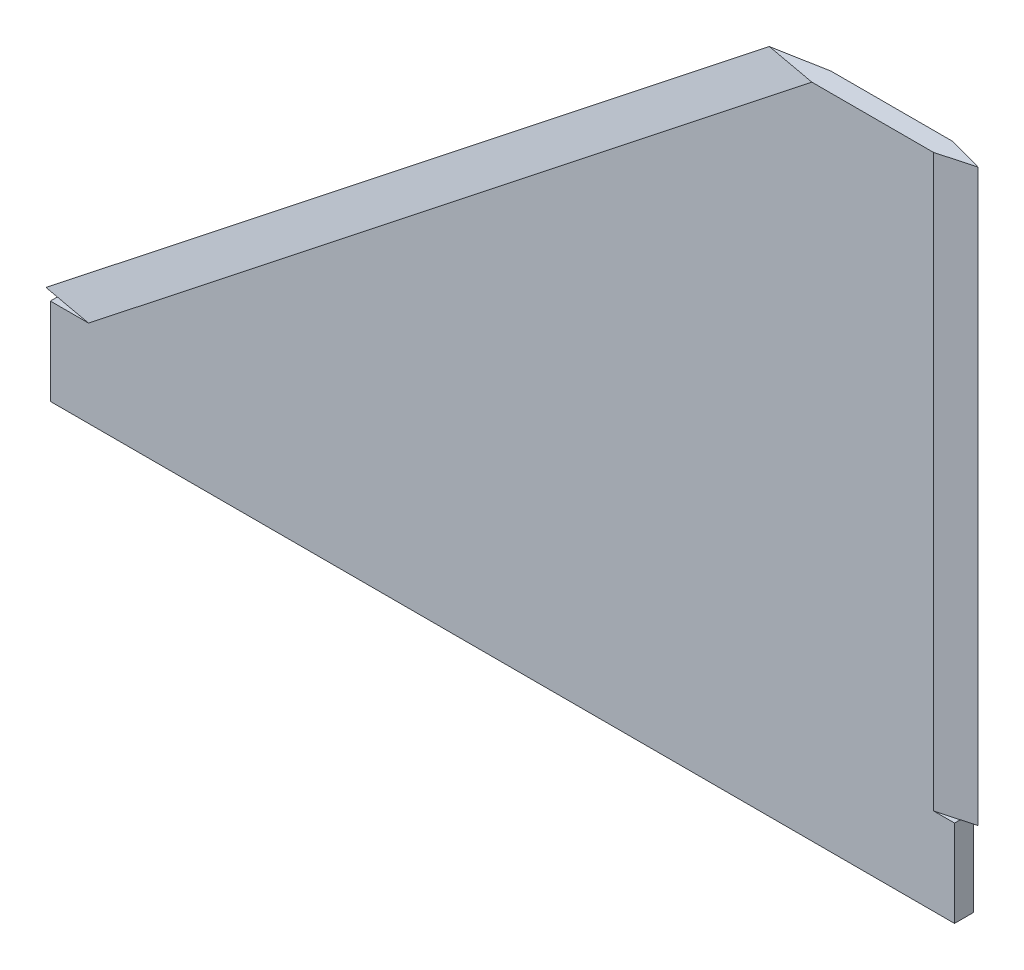
SolidWorks part; units mm, degrees
material "Hexcel AS4C (3000 Filaments)"
ref_plane "Front Plane" through (0, 0, 0) normal (0, 0, 1) x (1, 0, 0)
ref_plane "Top Plane" through (0, 0, 0) normal (0, 1, 0) x (1, 0, 0)
ref_plane "Right Plane" through (0, 0, 0) normal (1, 0, 0) x (0, 0, -1)
sketch "Sketch1" plane through (0, 0, 0) normal (0, 0, 1) x (1, 0, 0)
  line L0 (-130, 0) -> (-134, 0)
  line L1 (-130, -25) -> (130, -25)
  line L2 (-130, -25) -> (-130, 0)
  line L4 (130, -25) -> (130, 0)
  line L5 (-134, 0) -> (74, 164)
  line L6 (74, 164) -> (134, 164)
  line L7 (134, 164) -> (134, 0)
  line L8 (134, 0) -> (130, 0)
  line L9 (-130, 0) -> (130, 0)
  point P4 (-134.3185, 0)
  dimension "D1" = 25
  dimension "D2" = 268
  dimension "D3" = 260
  dimension "D4" = 164
  dimension "D5" = 60
extrude "Boss-Extrude1" add sketch "Sketch1" along normal blind 2.75 and the other way blind 2.75 contours L9 L2 L1 L4 | L0 L9 L8 L7 L6 L5 region at (0, -12.5, 0) region at (41.0081, 64.6667, 0)
sketch "Sketch2" plane through (0, 164, 0) normal (0, 1, 0) x (1, 0, 0)
  line L0 (74, 0) -> (89, -2.75)
  line L1 (74, 2.75) -> (74, -2.75) construction
  line L2 (74, -2.75) -> (134, -2.75) construction
  line L3 (89, -2.75) -> (74, -2.75)
  line L4 (74, -2.75) -> (74, 0)
  line L5 (74, 2.75) -> (74, 0)
  line L6 (89, 2.75) -> (74, 0)
  line L7 (74, 2.75) -> (134, 2.75) construction
  line L8 (74, 2.75) -> (89, 2.75)
  line L9 (89, 2.75) -> (89, -2.75) construction
  line M3 (74, 2.75) -> (74, -2.75)
  line M4 (74, -2.75) -> (134, -2.75)
  line M6 (134, 2.75) -> (74, 2.75)
  dimension "D1" = 15
extrude "Cut-Extrude1" cut sketch "Sketch2" along direction (0.7853, 0.6192, 0) on the side against the normal up to surface (164 mm away) contours L0 M3 M4 | L6 M6 M3 region at (79, 164, 1.8333) region at (79, 164, -1.8333) up to face at (132, 0, 0)
sketch "Sketch3" plane through (0, 164, 0) normal (0, 1, 0) x (1, 0, 0)
  line L0 (124, 2.75) -> (134, 2.75)
  line L1 (89, 2.75) -> (134, 2.75) construction
  line L2 (134, -2.75) -> (134, 0)
  line L3 (134, -2.75) -> (124, -2.75)
  line L4 (89, -2.75) -> (134, -2.75) construction
  line L5 (124, -2.75) -> (134, 0)
  line L6 (134, 0) -> (124, 2.75)
  line L7 (124, 2.75) -> (124, -2.75) construction
  line L8 (134, 2.75) -> (134, 0)
  line M5 (89, -2.75) -> (134, -2.75)
  line M6 (134, -2.75) -> (134, 2.75)
  line M7 (134, 2.75) -> (89, 2.75)
  dimension "D1" = 10
extrude "Cut-Extrude2" cut sketch "Sketch3" against normal up to surface (164 mm away) contours L5 M5 M6 | L6 M6 M7 region at (130.6667, 164, 1.8333) region at (130.6667, 164, -1.8333) up to face at (132, 0, 0)
